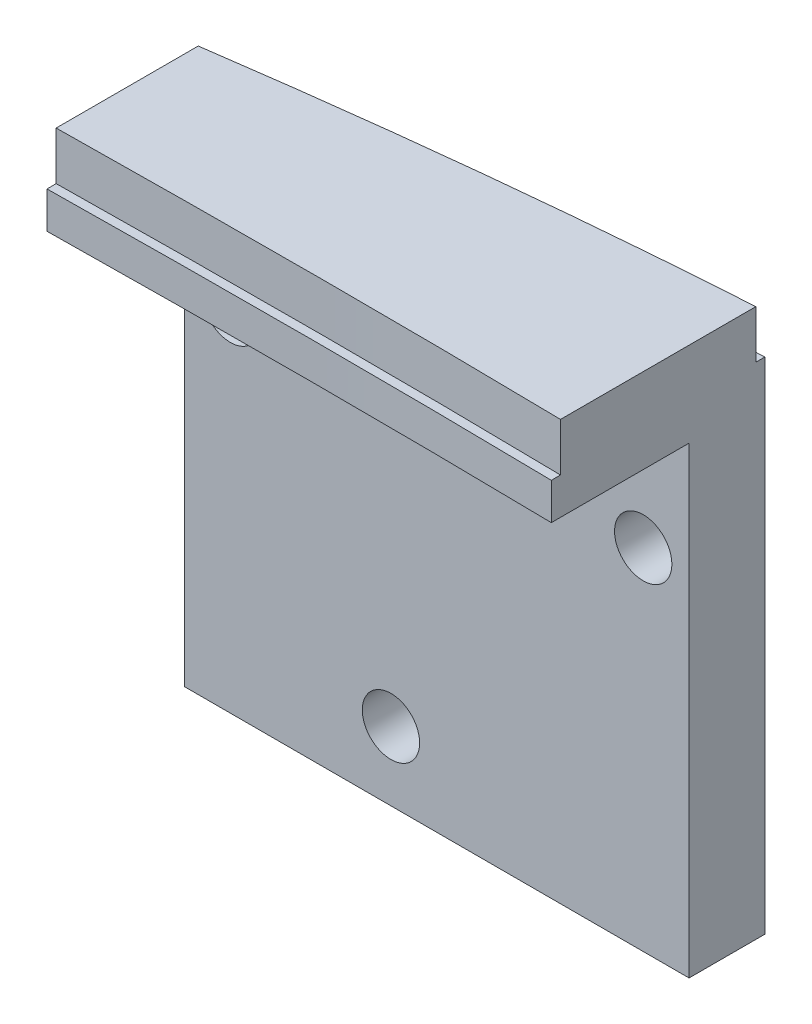
SolidWorks part; units mm, degrees
ref_plane "Front Plane" through (0, 0, 0) normal (0, 0, 1) x (1, 0, 0)
ref_plane "Top Plane" through (0, 0, 0) normal (0, 1, 0) x (1, 0, 0)
ref_plane "Right Plane" through (0, 0, 0) normal (1, 0, 0) x (0, 0, -1)
sketch "Sketch1" plane through (0, 0, 0) normal (0, 1, 0) x (1, 0, 0)
  line L0 (-144.1303, -12.9929) -> (155.8697, -12.8308) construction
  line L1 (-29.3738, 9.8314) -> (-29.3738, -4.1686)
  line L2 (14.6262, 14.4548) -> (14.6262, -4.183)
  line L5 (-29.3738, -2.9686) -> (14.6262, -2.9686)
  line L12 (-51.1303, 9.4041) -> (-59.1513, -7.7971) construction
  line L13 (-109.8536, -6.9996) -> (-109.986, -6.1605)
  circle A2 centre (-36.6303, 2.3202) radius 4.25
  arc A9 (-58.7697, -6.9788) -> (-58.7632, -6.9861) centre (-51.1303, -0.0856) ccw
  ellipse E0 centre (-36.6303, 2.3202) end of major axis (-36.1292, -4.0323) minor radius 5.05
  spline S0 degree 13 poles (-110.7235, -3.2524) (-98.8326, -0.2567) (-86.3944, 2.6358) (-73.4943, 5.427) (-60.2589, 8.0815) (-46.8275, 10.5453) (-33.3355, 12.7584) (-19.9065, 14.665) (-6.6486, 16.2187) (6.3449, 17.3865) (18.9944, 18.15) (31.2324, 18.5052) (43.0009, 18.4619) (54.25, 18.0415) knots 0.038912 0.038912 0.038912 0.038912 0.038912 0.038912 0.038912 0.038912 0.038912 0.038912 0.038912 0.038912 0.038912 0.038912 0.206425 0.206425 0.206425 0.206425 0.206425 0.206425 0.206425 0.206425 0.206425 0.206425 0.206425 0.206425 0.206425 0.206425
  spline S1 degree 3 poles (-105.7874, -5.9402) (-105.4515, -5.8576) (-103.7907, -5.4506) (-99.0842, -4.3142) (-91.5415, -2.5615) (-82.0457, -0.4684) (-69.1527, 2.2208) (-52.7063, 5.3568) (-32.7854, 8.6244) (-12.9944, 11.2716) (3.1558, 12.8711) (15.7533, 13.7541) (25.0163, 14.2135) (32.556, 14.4255) (38.4824, 14.4928) (41.3869, 14.4927) (42.8464, 14.4842) knots 0.043242 0.043242 0.043242 0.043242 0.044325 0.048583 0.058255 0.067926 0.077598 0.096941 0.116284 0.135628 0.154971 0.164642 0.174314 0.183986 0.188821 0.193657 0.193657 0.193657 0.193657
  spline S2 degree 3 poles (42.3412, -4.3021) (39.1703, -4.1474) (32.8439, -3.8739) (20.0493, -3.4589) (3.9637, -3.1861) (-15.3945, -3.1849) (-34.7131, -3.4228) (-53.9413, -3.8315) (-69.8279, -4.2978) (-82.3956, -4.7634) (-91.7251, -5.1693) (-99.1578, -5.5509) (-103.8174, -5.8207) (-105.4427, -5.9191) (-105.7874, -5.9402) knots 0.702444 0.702444 0.702444 0.702444 0.71714 0.731836 0.761227 0.790619 0.820011 0.849403 0.878795 0.89349 0.908186 0.922882 0.929138 0.930826 0.930826 0.930826 0.930826
  spline S3 degree 3 poles (-109.986, -6.1605) (-109.4642, -6.0291) (-108.4175, -5.7667) (-103.5943, -4.5692) (-94.8971, -2.4925) (-82.0108, 0.3758) (-63.7471, 4.1371) (-40.3543, 8.3552) (-16.9896, 11.6162) (1.2883, 13.4985) (14.7075, 14.5233) (27.7627, 15.1448) (36.8021, 15.2972) (42.0404, 15.2892) (43.1567, 15.2825) (43.6671, 15.2784) knots 0.038912 0.038912 0.038912 0.038912 0.040616 0.04232 0.054528 0.06816 0.081792 0.109056 0.13632 0.149952 0.163584 0.177216 0.190848 0.192861 0.194565 0.194565 0.194565 0.194565
  spline S4 degree 13 poles (52.5193, -8.6666) (40.2713, -7.9192) (27.7839, -7.3485) (15.1503, -6.9773) (2.4425, -6.804) (-10.2886, -6.8041) (-23.0116, -6.9375) (-35.7087, -7.1592) (-48.3688, -7.4339) (-60.9767, -7.7494) (-73.5011, -8.1244) (-85.8777, -8.6024) (-97.9897, -9.2254) (-109.6522, -9.993) knots 0.686195 0.686195 0.686195 0.686195 0.686195 0.686195 0.686195 0.686195 0.686195 0.686195 0.686195 0.686195 0.686195 0.686195 0.937578 0.937578 0.937578 0.937578 0.937578 0.937578 0.937578 0.937578 0.937578 0.937578 0.937578 0.937578 0.937578 0.937578
  spline S5 degree 3 poles (-110.5235, -4.0272) (-108.9029, -3.6189) (-105.6763, -2.8183) (-99.0735, -1.2268) (-90.6514, 0.7176) (-80.2925, 2.9758) (-67.9991, 5.4979) (-58.7506, 7.2436) (-50.652, 8.6798) (-47.6807, 9.1904) (-44.5606, 9.7093) (-38.2765, 10.745) (-25.0157, 12.7601) (-5.2278, 15.1631) (12.1229, 16.5847) (25.5727, 17.2429) (35.4177, 17.4948) (43.3901, 17.504) (49.633, 17.3925) (52.6803, 17.2987) (54.2127, 17.2415) knots 0.038912 0.038912 0.038912 0.038912 0.044146 0.049381 0.059851 0.07032 0.08079 0.096446 0.097403 0.1044 0.105092 0.106475 0.122668 0.143607 0.164546 0.175016 0.185486 0.195955 0.20119 0.206425 0.206425 0.206425 0.206425
  spline S6 degree 3 poles (52.5681, -7.868) (50.9024, -7.7664) (47.578, -7.5733) (40.8667, -7.2231) (32.4163, -6.8574) (22.195, -6.5335) (8.4979, -6.2488) (-8.6998, -6.1472) (-26.1679, -6.3047) (-37.8303, -6.5029) (-44.675, -6.6412) (-49.0049, -6.7375) (-53.5282, -6.8475) (-56.9797, -6.937) (-62.6027, -7.0912) (-70.3002, -7.3251) (-80.3346, -7.6831) (-90.3076, -8.1048) (-98.4897, -8.5174) (-104.9445, -8.8903) (-108.1134, -9.09) (-109.7048, -9.1947) knots 0.686195 0.686195 0.686195 0.686195 0.69405 0.701906 0.717617 0.733329 0.74904 0.780463 0.811886 0.82883 0.833892 0.843309 0.848739 0.854731 0.859237 0.874732 0.890444 0.906155 0.921867 0.929722 0.937578 0.937578 0.937578 0.937578
  spline S7 degree 3 poles (43.1189, -5.1414) (42.5664, -5.1139) (40.3515, -5.0059) (33.6908, -4.7068) (23.0612, -4.3421) (5.0464, -3.9837) (-17.5716, -3.9643) (-44.6283, -4.3923) (-66.9803, -4.9899) (-84.5965, -5.6437) (-96.3916, -6.1935) (-104.7586, -6.6717) (-108.8142, -6.9312) (-109.8536, -6.9996) knots 0.701175 0.701175 0.701175 0.701175 0.703751 0.711493 0.7321 0.752708 0.793923 0.835139 0.876354 0.896962 0.917569 0.932426 0.937578 0.937578 0.937578 0.937578
  spline S8 degree 3 poles (43.0791, -5.9404) (39.8994, -5.7822) (33.5559, -5.5021) (20.7207, -5.0752) (4.577, -4.7906) (-14.8622, -4.781) (-29.9542, -4.963) (-38.7515, -5.1226) (-41.4966, -5.1769) (-43.935, -5.226) (-46.8305, -5.2883) (-49.9812, -5.3611) (-51.9548, -5.4083) (-59.5635, -5.5969) (-69.6735, -5.894) (-82.18, -6.356) (-91.5501, -6.7627) (-99.2415, -7.157) (-105.3139, -7.5106) (-108.2984, -7.6991) (-109.7967, -7.7977) knots 0.701175 0.701175 0.701175 0.701175 0.71595 0.730726 0.760276 0.789826 0.819377 0.829214 0.830132 0.831967 0.840401 0.843428 0.846456 0.849484 0.878477 0.893252 0.908028 0.922803 0.93019 0.937578 0.937578 0.937578 0.937578
  spline S9 degree 3 poles (-110.1814, -5.3848) (-108.6794, -5.0063) (-105.6878, -4.2632) (-99.5742, -2.785) (-91.7846, -0.9758) (-82.2124, 1.1324) (-69.613, 3.7573) (-59.5108, 5.6872) (-50.135, 7.3499) (-46.7114, 7.9355) (-40.1955, 9.0106) (-29.5503, 10.6773) (-12.6029, 12.9298) (3.6765, 14.5228) (16.3735, 15.3941) (25.7087, 15.8415) (33.3064, 16.0409) (39.2778, 16.0967) (42.204, 16.0903) (43.6745, 16.0785) knots 0.038912 0.038912 0.038912 0.038912 0.043776 0.04864 0.058368 0.068097 0.077825 0.096092 0.09776 0.105207 0.106069 0.116738 0.136195 0.155652 0.16538 0.175108 0.184837 0.189701 0.194565 0.194565 0.194565 0.194565
  dimension "D1" = 8.5
  dimension "D2" = 14
  dimension "D3" = 44
  dimension "D4" = 1.2
extrude "Boss-Extrude2" add sketch "Sketch1" against normal blind 47.8 contours S3 L1 S1 L2 | S1 L1 L5 L2 | S2 L2 L5 L1 | S7 L2 S2 L1 region at (-7.4038, 0, -12.035) region at (-6.2065, 0, -4.396) region at (-7.397, 0, 3.1176) region at (-7.3732, 0, 3.6567)
extrude "Cut-Extrude1" cut sketch "Sketch1<3>" against normal blind 4.2 contours S7 L2 S2 L1 | S3 L1 S1 L2 region at (-7.4038, 0, -12.035) region at (-7.3732, 0, 3.6567)
sketch "Sketch1<3>" plane through (0, 0, 0) normal (0, 1, 0) x (1, 0, 0) same geometry as "Sketch1"
sketch "Sketch2" plane through (0, 0, 0) normal (0, 1, 0) x (1, 0, 0)
  line L0 (-29.3738, 7.8314) -> (14.6262, 7.8314)
  line L1 (-29.3738, 9.8314) -> (-29.3738, -4.1686) construction
  line L2 (14.6262, 14.4548) -> (14.6262, -4.183) construction
  line L3 (-29.3738, -2.9686) -> (14.6262, -2.9686) construction
  line L4 (-29.3738, -2.9686) -> (14.6262, -2.9686)
  line L5 (14.6262, 14.4548) -> (14.6262, -4.183)
  line L6 (-29.3738, 9.8314) -> (-29.3738, -4.1686)
  spline S0 degree 3 poles (-947.9599, -138.3998) (370.8641, -85.6061) (232.6754, -13.6415) (33.6908, -4.7068) (23.0612, -4.3421) (5.0464, -3.9837) (-17.5716, -3.9643) (-44.6283, -4.3923) (-66.9803, -4.9899) (-84.5965, -5.6437) (-96.3916, -6.1935) (-248.8544, -14.9069) (-311.486, -54.3396) (882.4768, -130.5168) knots -0.19176 -0.19176 -0.19176 -0.19176 0.703751 0.711493 0.7321 0.752708 0.793923 0.835139 0.876354 0.896962 0.917569 0.932426 1.637069 1.637069 1.637069 1.637069 only from (43.1189, -5.1414) to (-109.8536, -6.9996) construction
  spline S1 degree 3 poles (43.1189, -5.1414) (42.5664, -5.1139) (40.3515, -5.0059) (33.6908, -4.7068) (23.0612, -4.3421) (5.0464, -3.9837) (-17.5716, -3.9643) (-44.6283, -4.3923) (-66.9803, -4.9899) (-84.5965, -5.6437) (-96.3916, -6.1935) (-104.7586, -6.6717) (-108.8142, -6.9312) (-109.8536, -6.9996) knots 0.701175 0.701175 0.701175 0.701175 0.703751 0.711493 0.7321 0.752708 0.793923 0.835139 0.876354 0.896962 0.917569 0.932426 0.937578 0.937578 0.937578 0.937578
  point P8 (0, 0)
  spline M3 degree 3 poles (-105.7874, -5.9402) (-105.4427, -5.9191) (-103.8174, -5.8207) (-99.1578, -5.5509) (-91.7251, -5.1693) (-82.3956, -4.7634) (-69.8279, -4.2978) (-53.9413, -3.8315) (-34.7131, -3.4228) (-15.3945, -3.1849) (3.9637, -3.1861) (20.0493, -3.4589) (32.8439, -3.8739) (39.1703, -4.1474) (42.3412, -4.3021) knots 0.702444 0.702444 0.702444 0.702444 0.704132 0.710388 0.725084 0.739779 0.754475 0.783867 0.813259 0.842651 0.872042 0.901434 0.91613 0.930826 0.930826 0.930826 0.930826 only from (-29.3738, -3.3687) to (14.6262, -3.383)
  line M4 (14.6262, -3.383) -> (14.6262, 13.6533)
  line M6 (-29.3738, 9.0233) -> (-29.3738, -3.3687)
  dimension "D1" = 2
extrude "Cut-Extrude2" cut sketch "Sketch2" against normal through all from offset 7.4 contours L4 L0 M6 M4 | L4 M6 M3 M4 | S1 L5 L6 M3 region at (-7.3738, 0, -2.4314) region at (-7.3795, 0, 3.5139) offset against normal yes
sketch "Sketch3" plane through (0, 0, -7.8314) normal (0, 0, 1) x (1, 0, 0)
  line L0 (14.6262, -47.8) -> (14.6262, -7.4) construction
  line L1 (-29.3738, -47.8) -> (14.6262, -47.8) construction
  circle A0 centre (-11.3738, -41.8) radius 2.5
  circle A1 centre (-25.3738, -17.3) radius 2.5
  circle A2 centre (10.6262, -17.3) radius 2.5
  dimension "D1" = 5
  dimension "D2" = 14
  dimension "D3" = 36
  dimension "D4" = 4
  dimension "D5" = 24.5
  dimension "D6" = 6
extrude "Cut-Extrude3" cut sketch "Sketch3" against normal through all
